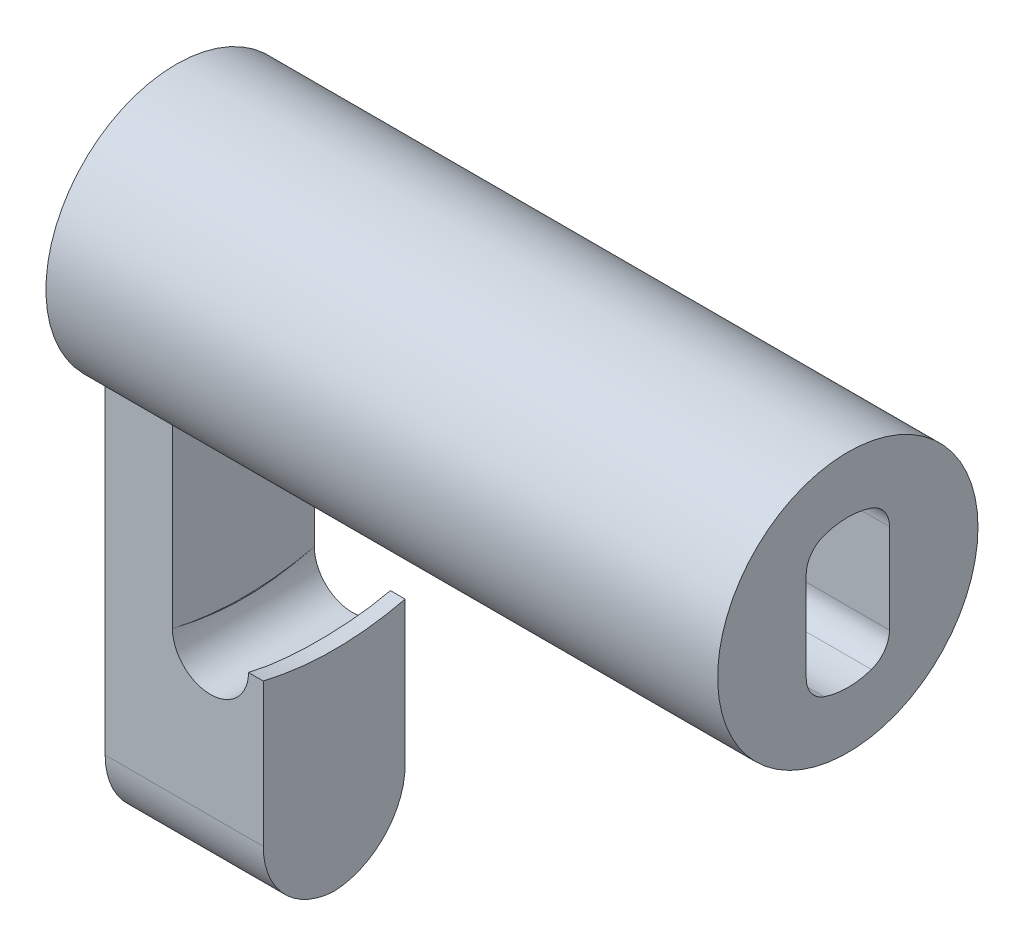
SolidWorks part; units mm, degrees
material "ABS"
ref_plane "Front Plane" through (0, 0, 0) normal (1, 0, 0) x (0, 1, 0)
ref_plane "Top Plane" through (0, 0, 0) normal (0, 0, 1) x (0, 1, 0)
ref_plane "Right Plane" through (0, 0, 0) normal (0, 1, 0) x (-1, 0, 0)
sketch "Sketch1" plane through (0, 0, 0) normal (1, 0, 0) x (0, 1, 0)
  circle A2 centre (0, 0) radius 8.7376
  dimension "D3" = 17.4752
extrude "Boss-Extrude1" add sketch "Sketch1" along normal blind 45.085
sketch "Sketch10" plane through (0, 0, 0) normal (-1, 0, 0) x (0, -1, 0)
  line L0 (7.3256, 4.7625) -> (34.036, 4.7625)
  line L2 (34.036, 4.7625) -> (34.036, -4.7625)
  line L3 (34.036, -4.7625) -> (7.3256, -4.7625)
  circle A0 centre (0, 0) radius 8.7376 construction
  arc A2 (7.3256, 4.7625) -> (7.3256, -4.7625) centre (0, 0) cw
  point P2 (34.036, 0)
  dimension "D1" = 34.036
  dimension "D2" = 9.525
extrude "Boss-Extrude3" add sketch "Sketch10" against normal blind 4.516 contours L0 A2 L3 L2
fillet "Fillet2" radius 5 2 edges at (2.258, -34.036, 4.7625) (2.258, -34.036, -4.7625)
sketch "Sketch14" [suppressed] plane through (0, 0, 0) normal (-1, 0, 0) x (0, 0, 1)
  line L0 (0.5115, -3.4237) -> (0.3944, -4.0089)
  line L1 (0, 0) -> (0, -4.064) construction
  line L2 (0, 0) -> (0.5606, -3.4335) construction
  line L3 (0.6039, -3.4087) -> (0.9011, -3.9262)
  line L4 (-0.6903, -3.3922) -> (-1.0005, -3.9021)
  line L5 (-0.5983, -3.4096) -> (-0.4961, -3.9976)
  line L6 (-1.8089, -2.9515) -> (-2.2748, -3.3245)
  line L7 (-1.7284, -2.9994) -> (-1.8334, -3.5869)
  line L8 (-2.7093, -2.1549) -> (-3.2746, -2.346)
  line L9 (-2.65, -2.2273) -> (-2.9496, -2.7435)
  line L10 (-3.2829, -1.0983) -> (-3.8795, -1.0846)
  line L11 (-3.252, -1.1867) -> (-3.7101, -1.5692)
  line L12 (-3.4605, 0.0907) -> (-4.0165, 0.3077)
  line L13 (-3.4617, -0.0029) -> (-4.023, -0.2057)
  line L14 (-3.2208, 1.2689) -> (-3.669, 1.6629)
  line L15 (-3.2539, 1.1813) -> (-3.8507, 1.1827)
  line L16 (-2.5926, 2.2939) -> (-2.879, 2.8175)
  line L17 (-2.6537, 2.223) -> (-3.214, 2.4284)
  line L18 (-1.6517, 3.0423) -> (-1.7417, 3.6323)
  line L19 (-1.7333, 2.9965) -> (-2.1896, 3.3812)
  line L20 (-0.5115, 3.4237) -> (-0.3944, 4.0089)
  line L21 (-0.6039, 3.4087) -> (-0.9011, 3.9262)
  line L22 (0.6903, 3.3922) -> (1.0005, 3.9021)
  line L23 (0.5983, 3.4096) -> (0.4961, 3.9976)
  line L24 (1.8089, 2.9515) -> (2.2748, 3.3245)
  line L25 (1.7284, 2.9994) -> (1.8334, 3.5869)
  line L26 (2.7093, 2.1549) -> (3.2746, 2.346)
  line L27 (2.65, 2.2273) -> (2.9496, 2.7435)
  line L28 (3.2829, 1.0983) -> (3.8795, 1.0846)
  line L29 (3.252, 1.1867) -> (3.7101, 1.5692)
  line L30 (3.4605, -0.0907) -> (4.0165, -0.3077)
  line L31 (3.4617, 0.0029) -> (4.023, 0.2057)
  line L32 (3.2208, -1.2689) -> (3.669, -1.6629)
  line L33 (3.2539, -1.1813) -> (3.8507, -1.1827)
  line L34 (2.5926, -2.2939) -> (2.879, -2.8175)
  line L35 (2.6537, -2.223) -> (3.214, -2.4284)
  line L36 (1.6517, -3.0423) -> (1.7417, -3.6323)
  line L37 (1.7333, -2.9965) -> (2.1896, -3.3812)
  line L38 (-0.1032, -4.0627) -> (0, -4.064)
  line L39 (-1.4865, -3.7824) -> (-1.39, -3.8189)
  line L40 (-2.6905, -3.0459) -> (-2.6123, -3.1132)
  line L41 (-3.5195, -2.032) -> (-3.57, -1.942)
  line L42 (-4.0023, -0.7057) -> (-4.0189, -0.6039)
  line L43 (-4.0023, 0.7057) -> (-3.9831, 0.8071)
  line L44 (-3.5195, 2.032) -> (-3.4668, 2.1207)
  line L45 (-2.6123, 3.1132) -> (-2.5324, 3.1785)
  line L46 (-1.39, 3.8189) -> (-1.2926, 3.853)
  line L47 (0, 4.064) -> (0.1032, 4.0627)
  line L48 (1.39, 3.8189) -> (1.4865, 3.7824)
  line L49 (2.6123, 3.1132) -> (2.6905, 3.0459)
  line L50 (3.5195, 2.032) -> (3.57, 1.942)
  line L51 (4.0023, 0.7057) -> (4.0189, 0.6039)
  line L52 (4.0023, -0.7057) -> (3.9831, -0.8071)
  line L53 (3.5195, -2.032) -> (3.4668, -2.1207)
  line L54 (2.6123, -3.1132) -> (2.5324, -3.1785)
  line L55 (1.39, -3.8189) -> (1.2926, -3.853)
  arc A0 (0.3497, -4.0489) -> (0, -4.064) centre (0, 0) cw
  arc A1 (0.3497, -4.0489) -> (0.3944, -4.0089) centre (0.3454, -3.9991) ccw
  arc A2 (0.5115, -3.4237) -> (0.6039, -3.4087) centre (0.5606, -3.4335) cw
  arc A3 (0.4203, -4.0631) -> (0.3944, -4.0089) centre (0.4434, -4.0187) cw
  arc A4 (0.4203, -4.0631) -> (0.7372, -4.2116) centre (2.3016, -0.4608) ccw
  arc A6 (0.9562, -3.9499) -> (0.9011, -3.9262) centre (0.9445, -3.9013) cw
  arc A7 (0.9562, -3.9499) -> (1.2926, -3.853) centre (0, 0) ccw
  arc A8 (-1.0562, -3.9243) -> (-1.39, -3.8189) centre (0, 0) cw
  arc A9 (-1.0562, -3.9243) -> (-1.0005, -3.9021) centre (-1.0432, -3.8761) ccw
  arc A10 (-0.6903, -3.3922) -> (-0.5983, -3.4096) centre (-0.6476, -3.4182) cw
  arc A11 (-0.4524, -4.0387) -> (-0.4961, -3.9976) centre (-0.4468, -3.9891) cw
  arc A12 (-0.4524, -4.0387) -> (-0.1032, -4.0627) centre (0, 0) ccw
  arc A13 (-2.3347, -3.3264) -> (-2.6123, -3.1132) centre (0, 0) cw
  arc A14 (-2.3347, -3.3264) -> (-2.2748, -3.3245) centre (-2.306, -3.2855) ccw
  arc A15 (-1.8089, -2.9515) -> (-1.7284, -2.9994) centre (-1.7776, -2.9906) cw
  arc A16 (-1.8064, -3.6405) -> (-1.8334, -3.5869) centre (-1.7842, -3.5957) cw
  arc A17 (-1.8064, -3.6405) -> (-1.4865, -3.7824) centre (0, 0) ccw
  arc A18 (-3.3316, -2.3273) -> (-3.5195, -2.032) centre (0, 0) cw
  arc A19 (-3.3316, -2.3273) -> (-3.2746, -2.346) centre (-3.2906, -2.2987) ccw
  arc A20 (-2.7093, -2.1549) -> (-2.65, -2.2273) centre (-2.6933, -2.2022) cw
  arc A21 (-2.9426, -2.8031) -> (-2.9496, -2.7435) centre (-2.9064, -2.7686) cw
  arc A22 (-2.9426, -2.8031) -> (-2.6905, -3.0459) centre (0, 0) ccw
  arc A23 (-3.9267, -1.0475) -> (-4.0023, -0.7057) centre (0, 0) cw
  arc A24 (-3.9267, -1.0475) -> (-3.8795, -1.0846) centre (-3.8784, -1.0346) ccw
  arc A25 (-3.2829, -1.0983) -> (-3.252, -1.1867) centre (-3.284, -1.1483) cw
  arc A26 (-3.7238, -1.6276) -> (-3.7101, -1.5692) centre (-3.678, -1.6076) cw
  arc A27 (-3.7238, -1.6276) -> (-3.57, -1.942) centre (0, 0) ccw
  arc A28 (-4.0481, 0.3587) -> (-4.0023, 0.7057) centre (0, 0) cw
  arc A29 (-4.0481, 0.3587) -> (-4.0165, 0.3077) centre (-3.9983, 0.3543) ccw
  arc A30 (-3.4605, 0.0907) -> (-3.4617, -0.0029) centre (-3.4787, 0.0442) cw
  arc A31 (-4.0559, -0.2558) -> (-4.023, -0.2057) centre (-4.006, -0.2527) cw
  arc A32 (-4.0559, -0.2558) -> (-4.0189, -0.6039) centre (0, 0) ccw
  arc A33 (-3.6813, 1.7216) -> (-3.5195, 2.032) centre (0, 0) cw
  arc A34 (-3.6813, 1.7216) -> (-3.669, 1.6629) centre (-3.636, 1.7005) ccw
  arc A35 (-3.2208, 1.2689) -> (-3.2539, 1.1813) centre (-3.2538, 1.2313) cw
  arc A36 (-3.8988, 1.1468) -> (-3.8507, 1.1827) centre (-3.8509, 1.1327) cw
  arc A37 (-3.8988, 1.1468) -> (-3.9831, 0.8071) centre (0, 0) ccw
  arc A38 (-2.8705, 2.8769) -> (-2.6123, 3.1132) centre (0, 0) cw
  arc A39 (-2.8705, 2.8769) -> (-2.879, 2.8175) centre (-2.8352, 2.8415) ccw
  arc A40 (-2.5926, 2.2939) -> (-2.6537, 2.223) centre (-2.6365, 2.2699) cw
  arc A41 (-3.2715, 2.4111) -> (-3.214, 2.4284) centre (-3.2312, 2.3815) cw
  arc A42 (-3.2715, 2.4111) -> (-3.4668, 2.1207) centre (0, 0) ccw
  arc A43 (-1.7134, 3.6852) -> (-1.39, 3.8189) centre (0, 0) cw
  arc A44 (-1.7134, 3.6852) -> (-1.7417, 3.6323) centre (-1.6923, 3.6398) ccw
  arc A45 (-1.6517, 3.0423) -> (-1.7333, 2.9965) centre (-1.7011, 3.0348) cw
  arc A46 (-2.2495, 3.3846) -> (-2.1896, 3.3812) centre (-2.2218, 3.343) cw
  arc A47 (-2.2495, 3.3846) -> (-2.5324, 3.1785) centre (0, 0) ccw
  arc A48 (-0.3497, 4.0489) -> (0, 4.064) centre (0, 0) cw
  arc A49 (-0.3497, 4.0489) -> (-0.3944, 4.0089) centre (-0.3454, 3.9991) ccw
  arc A50 (-0.5115, 3.4237) -> (-0.6039, 3.4087) centre (-0.5606, 3.4335) cw
  arc A51 (-0.9562, 3.9499) -> (-0.9011, 3.9262) centre (-0.9445, 3.9013) cw
  arc A52 (-0.9562, 3.9499) -> (-1.2926, 3.853) centre (0, 0) ccw
  arc A53 (1.0562, 3.9243) -> (1.39, 3.8189) centre (0, 0) cw
  arc A54 (1.0562, 3.9243) -> (1.0005, 3.9021) centre (1.0432, 3.8761) ccw
  arc A55 (0.6903, 3.3922) -> (0.5983, 3.4096) centre (0.6476, 3.4182) cw
  arc A56 (0.4524, 4.0387) -> (0.4961, 3.9976) centre (0.4468, 3.9891) cw
  arc A57 (0.4524, 4.0387) -> (0.1032, 4.0627) centre (0, 0) ccw
  arc A58 (2.3347, 3.3264) -> (2.6123, 3.1132) centre (0, 0) cw
  arc A59 (2.3347, 3.3264) -> (2.2748, 3.3245) centre (2.306, 3.2855) ccw
  arc A60 (1.8089, 2.9515) -> (1.7284, 2.9994) centre (1.7776, 2.9906) cw
  arc A61 (1.8064, 3.6405) -> (1.8334, 3.5869) centre (1.7842, 3.5957) cw
  arc A62 (1.8064, 3.6405) -> (1.4865, 3.7824) centre (0, 0) ccw
  arc A63 (3.3316, 2.3273) -> (3.5195, 2.032) centre (0, 0) cw
  arc A64 (3.3316, 2.3273) -> (3.2746, 2.346) centre (3.2906, 2.2987) ccw
  arc A65 (2.7093, 2.1549) -> (2.65, 2.2273) centre (2.6933, 2.2022) cw
  arc A66 (2.9426, 2.8031) -> (2.9496, 2.7435) centre (2.9064, 2.7686) cw
  arc A67 (2.9426, 2.8031) -> (2.6905, 3.0459) centre (0, 0) ccw
  arc A68 (3.9267, 1.0475) -> (4.0023, 0.7057) centre (0, 0) cw
  arc A69 (3.9267, 1.0475) -> (3.8795, 1.0846) centre (3.8784, 1.0346) ccw
  arc A70 (3.2829, 1.0983) -> (3.252, 1.1867) centre (3.284, 1.1483) cw
  arc A71 (3.7238, 1.6276) -> (3.7101, 1.5692) centre (3.678, 1.6076) cw
  arc A72 (3.7238, 1.6276) -> (3.57, 1.942) centre (0, 0) ccw
  arc A73 (4.0481, -0.3587) -> (4.0023, -0.7057) centre (0, 0) cw
  arc A74 (4.0481, -0.3587) -> (4.0165, -0.3077) centre (3.9983, -0.3543) ccw
  arc A75 (3.4605, -0.0907) -> (3.4617, 0.0029) centre (3.4787, -0.0442) cw
  arc A76 (4.0559, 0.2558) -> (4.023, 0.2057) centre (4.006, 0.2527) cw
  arc A77 (4.0559, 0.2558) -> (4.0189, 0.6039) centre (0, 0) ccw
  arc A78 (3.6813, -1.7216) -> (3.5195, -2.032) centre (0, 0) cw
  arc A79 (3.6813, -1.7216) -> (3.669, -1.6629) centre (3.636, -1.7005) ccw
  arc A80 (3.2208, -1.2689) -> (3.2539, -1.1813) centre (3.2538, -1.2313) cw
  arc A81 (3.8988, -1.1468) -> (3.8507, -1.1827) centre (3.8509, -1.1327) cw
  arc A82 (3.8988, -1.1468) -> (3.9831, -0.8071) centre (0, 0) ccw
  arc A83 (2.8705, -2.8769) -> (2.6123, -3.1132) centre (0, 0) cw
  arc A84 (2.8705, -2.8769) -> (2.879, -2.8175) centre (2.8352, -2.8415) ccw
  arc A85 (2.5926, -2.2939) -> (2.6537, -2.223) centre (2.6365, -2.2699) cw
  arc A86 (3.2715, -2.4111) -> (3.214, -2.4284) centre (3.2312, -2.3815) cw
  arc A87 (3.2715, -2.4111) -> (3.4668, -2.1207) centre (0, 0) ccw
  arc A88 (1.7134, -3.6852) -> (1.39, -3.8189) centre (0, 0) cw
  arc A89 (1.7134, -3.6852) -> (1.7417, -3.6323) centre (1.6923, -3.6398) ccw
  arc A90 (1.6517, -3.0423) -> (1.7333, -2.9965) centre (1.7011, -3.0348) cw
  arc A91 (2.2495, -3.3846) -> (2.1896, -3.3812) centre (2.2218, -3.343) cw
  arc A92 (2.2495, -3.3846) -> (2.5324, -3.1785) centre (0, 0) ccw
  point P207 (0, 0)
  dimension "D1" = 4.064
  dimension "D2" = 0.05
  dimension "D3" = 0.05
  dimension "D4" = 0.04
  dimension "D5" = 18
  dimension "D6" = 0.5968
  dimension "D8" = 0.35
sketch "Sketch15" plane through (4.516, 0, 0) normal (1, 0, 0) x (0, 1, 0)
  line L4 (-18.7904, 4.7625) -> (-18.7904, -4.7625)
  line L10 (-7.3256, 4.7625) -> (-29.036, 4.7625)
  line L11 (-29.036, -4.7625) -> (-7.3256, -4.7625)
  line L12 (-18.7904, 4.7625) -> (-29.036, 4.7625)
  line L14 (-29.036, -4.7625) -> (-18.7904, -4.7625)
  arc A13 (-29.036, 4.7625) -> (-34.0304, 0) centre (-29.036, -0.2375) ccw
  arc A14 (-34.0304, 0) -> (-29.036, -4.7625) centre (-29.036, 0.2375) ccw
  arc A15 (-7.3256, 4.7625) -> (-7.3256, -4.7625) centre (0, 0) ccw
  arc A16 (-29.036, 4.7625) -> (-34.0304, 0) centre (-29.036, -0.2375) ccw
  arc A17 (-34.0304, 0) -> (-29.036, -4.7625) centre (-29.036, 0.2375) ccw
  dimension "D1" = 0
  dimension "D3" = 15.24
extrude "Boss-Extrude4" add sketch "Sketch15" along normal blind 6.096
sketch "Sketch21" plane through (10.612, 0, 0) normal (1, 0, 0) x (0, 1, 0)
  line L2 (-18.7904, -4.7625) -> (-18.7904, 4.7625)
  line L5 (-19.4254, -4.7625) -> (-18.7904, -4.7625)
  line L7 (-18.7904, 4.7625) -> (-18.7904, -4.7625) construction
  line L8 (-18.7904, -4.7625) -> (-7.3256, -4.7625) construction
  line L11 (-18.7904, 4.7625) -> (-29.036, 4.7625) construction
  line L14 (-18.7904, -4.7625) -> (-18.7904, 4.7625) construction
  line L20 (-18.7904, 4.7625) -> (-19.4254, 4.7625)
  arc A2 (-19.4254, -4.7625) -> (-19.4254, 4.7625) centre (0.3287, 0) cw
  point P8 (0, 0)
  point P9 (0, 0)
  point P10 (-19.7603, 8.7376)
  dimension "D4" = 20.32
  dimension "D2" = 0.635
  dimension "D3" = 0.635
extrude "Cut-Extrude8" cut sketch "Sketch21" against normal up to surface (6.096 mm away)
sketch "Sketch22" plane through (45.085, 0, 0) normal (1, 0, 0) x (0, 1, 0)
  line L7 (-4.0897, -2.794) -> (4.0897, 2.794) construction
  line L8 (-4.0897, 2.794) -> (4.0897, -2.794) construction
  line L11 (-4.0897, -2.794) -> (4.0897, -2.794)
  line L13 (-4.0897, 2.794) -> (4.0897, 2.794)
  line L15 (-4.0897, -2.794) -> (4.0897, 2.794) construction
  line L16 (-4.0897, 2.794) -> (4.0897, -2.794) construction
  arc A3 (-4.0897, 2.794) -> (-4.0897, -2.794) centre (0, 0) ccw
  arc A4 (4.0897, -2.794) -> (4.0897, 2.794) centre (0, 0) ccw
  dimension "D2" = 9.906
  dimension "D3" = 5.588
extrude "Cut-Extrude10" cut sketch "Sketch22" against normal blind 12.192
fillet "Fillet11" radius 1.778 4 edges at (38.989, 4.0897, -2.794) (38.989, 4.0897, 2.794) (38.989, -4.0897, -2.794) (38.989, -4.0897, 2.794)
sketch "Sketch25" plane through (0, 0, -4.7625) normal (0, 0, -1) x (1, 0, 0)
  line L3 (4.516, 19.4254) -> (4.516, 7.3256) construction
  line L4 (4.516, 19.4254) -> (10.612, 19.4254) construction
  circle A0 centre (7.0687, 19.4254) radius 2.5527
  dimension "D1" = 5.1054
extrude "Cut-Extrude14" cut sketch "Sketch25" against normal through all
sketch "Sketch26" plane through (0, 0, 0) normal (-1, 0, 0) x (0, -1, 0)
  line L1 (3.6846, 1.7145) -> (7.1771, 1.7145)
  line L2 (3.6846, 1.7145) -> (3.6846, -1.7145) construction
  line L3 (3.6846, -1.7145) -> (7.1771, -1.7145)
  line L4 (7.1771, 1.7145) -> (7.1771, -1.7145)
  arc A0 (3.6846, 1.7145) -> (3.6846, -1.7145) centre (0, 0) ccw
  dimension "D1" = 8.128
  dimension "D2" = 3.429
  dimension "D3" = 3.4925
extrude "Cut-Extrude15" cut sketch "Sketch26" against normal blind 9.525
fillet "Fillet12" radius 1.5875 4 edges at (4.7625, -3.6846, 1.7145) (4.7625, -7.1771, 1.7145) (4.7625, -3.6846, -1.7145) (4.7625, -7.1771, -1.7145)
